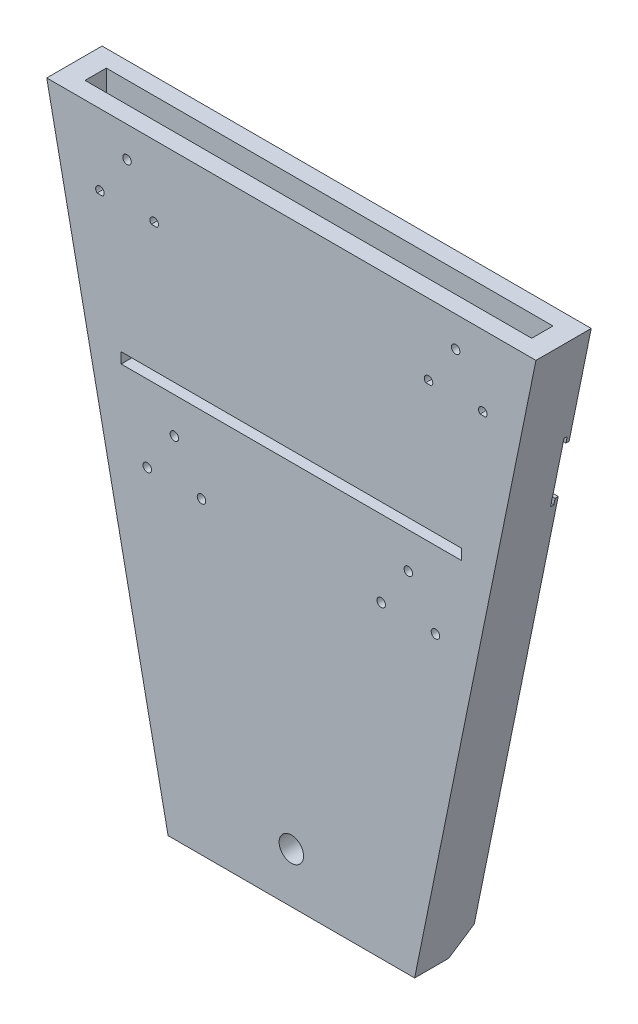
SolidWorks part; units mm, degrees
ref_plane "前视基准面" through (0, 0, 0) normal (0, 0, 1) x (1, 0, 0)
ref_plane "上视基准面" through (0, 0, 0) normal (0, 1, 0) x (1, 0, 0)
ref_plane "右视基准面" through (0, 0, 0) normal (1, 0, 0) x (0, 0, -1)
other "Configuration Table"
sketch "草图1" plane through (0, 0, 0) normal (0, 0, 1) x (1, 0, 0)
  line L0 (-60, 0) -> (60, 0)
  line L1 (0, 77.3448) -> (0, -71.5734) construction
  line L2 (-115, 270) -> (115, 270)
  line L3 (-115, 270) -> (-60, 0)
  line L4 (115, 270) -> (60, 0)
  point P3 (0, 0)
  point P8 (0, 270)
  dimension "D1" = 120
  dimension "D2" = 230
  dimension "D3" = 270
extrude "凸台-拉伸1" add sketch "草图1" along normal blind 8
sketch "草图2" plane through (0, 0, 8) normal (0, 0, 1) x (1, 0, 0)
  line L0 (-60, 0) -> (60, 0) construction
  line L1 (0, -1000) -> (0, 0.3) construction
  line L2 (0, 26.71) -> (0, 57.7278) construction
  line L3 (0.005, 0.31) -> (0, 0.3)
  line L4 (0, 26.71) -> (12.1089, 26.71)
  line L6 (0, 0.3) -> (17.4887, 0.3)
  line L7 (12.1089, 26.71) -> (17.4887, 0.3)
  line L8 (-115, 270) -> (-60, 0) construction
  arc A0 (0, 26.71) -> (0.005, 0.31) centre (0, 13.51) ccw
  dimension "D1" = 26.4
  dimension "D2" = 13.51
  dimension "D3" = 14.5
  dimension "D5" = 13.21
extrude "切除-拉伸1" cut sketch "草图2" against normal blind 8.6
sketch "草图3" plane through (0, 0, 8) normal (0, 0, 1) x (1, 0, 0)
  line L0 (-94.3261, 168.51) -> (94.3261, 168.51)
  line L1 (-115, 270) -> (-60, 0) construction
  line L2 (60, 0) -> (115, 270) construction
  line L4 (-96.3631, 178.51) -> (96.3631, 178.51)
  line L5 (-107.8704, 235) -> (107.8704, 235)
  point P0 (-115, 270)
  point P14 (0, 178.51)
  point P15 (0, 13.51)
  dimension "D1" = 155
  dimension "D2" = 10
  dimension "D3" = 35
sketch "草图5" plane through (0, 0, 0) normal (0, 0, -1) x (-1, 0, 0)
  line L4 (60, 0) -> (115, 270)
  line L5 (115, 270) -> (-115, 270)
  line L6 (-115, 270) -> (-60, 0)
  line L7 (-60, 0) -> (60, 0)
  line L8 (60, 0) -> (115, 270)
  line L9 (115, 270) -> (-115, 270)
  line L10 (-115, 270) -> (-60, 0)
  line L11 (-60, 0) -> (60, 0)
  dimension "D1" = 0
extrude "凸台-拉伸2" add sketch "草图5" along normal blind 8
sketch "草图6" plane through (0, 0, 8) normal (0, 0, 1) x (1, 0, 0)
  line L4 (-115, 270) -> (-60, 0)
  line L5 (-60, 0) -> (60, 0)
  line L6 (60, 0) -> (115, 270)
  line L7 (115, 270) -> (-115, 270)
  line L8 (-115, 270) -> (-60, 0)
  line L9 (-60, 0) -> (60, 0)
  line L10 (60, 0) -> (115, 270)
  line L11 (115, 270) -> (-115, 270)
  point P2 (0, 13.51)
  dimension "D1" = 0
extrude "凸台-拉伸3" add sketch "草图6" along normal blind 10
sketch "草图7" plane through (0, 0, 18) normal (0, 0, 1) x (1, 0, 0)
  circle A0 centre (0, 13.51) radius 5.75
  dimension "D1" = 11.5
extrude "切除-拉伸2" cut sketch "草图7" against normal blind 22
ref_plane "基准面1" through (0, 0, 18) normal (0, 0, 1) x (1, 0, 0)
sketch "草图9" plane through (0, 0, 18) normal (0, 0, 1) x (1, 0, 0)
  line L0 (-60, 0) -> (60, 0)
  line L1 (60, 0) -> (57.963, -10)
  line L2 (57.963, -10) -> (-57.963, -10)
  line L3 (-57.963, -10) -> (-60, 0)
  line L4 (60, 0) -> (115, 270) construction
  line L5 (-115, 270) -> (-60, 0) construction
  line L6 (60, 0) -> (115, 270)
  line L7 (-115, 270) -> (-60, 0)
  dimension "D1" = 10
extrude "凸台-拉伸5" add sketch "草图9" against normal blind 26 contours L3 L2 L1 L0 region at (0, -4.9712, 18)
ref_plane "基准面2" through (0, 0, -8) normal (0, 0, 1) x (1, 0, 0)
sketch "草图11" plane through (0, 0, -8) normal (0, 0, 1) x (1, 0, 0)
  line L0 (110.9179, 270) -> (53.8808, -10)
  line L1 (-110.9179, 270) -> (-53.8808, -10)
  line L2 (109.6932, 270) -> (52.6562, -10)
  line L3 (-109.6932, 270) -> (-52.6562, -10)
  line L4 (115, 270) -> (-115, 270)
  line L5 (-115, 270) -> (-57.963, -10)
  line L6 (-57.963, -10) -> (57.963, -10)
  line L7 (57.963, -10) -> (115, 270)
  line L8 (115, 270) -> (-115, 270)
  line L9 (-115, 270) -> (-57.963, -10)
  line L10 (-57.963, -10) -> (57.963, -10)
  line L11 (57.963, -10) -> (115, 270)
  dimension "D2" = 4
  dimension "D3" = 4
  dimension "D4" = 1.2
  dimension "D5" = 1.2
  dimension "D1" = 0
sketch "草图12" plane through (0, 0, -8) normal (0, 0, 1) x (1, 0, 0)
  line L0 (-115, 270) -> (-60, 0) construction
  line L1 (60, 0) -> (115, 270) construction
  line L2 (-115, 270) -> (-60, 0)
  line L3 (60, 0) -> (115, 270)
  line L4 (60, 0) -> (-60, 0)
  line L5 (57.963, -10) -> (60, 0)
  line L6 (-57.963, -10) -> (57.963, -10)
  line L7 (-60, 0) -> (-57.963, -10)
  line L8 (60, 0) -> (-60, 0)
  line L9 (57.963, -10) -> (60, 0)
  line L10 (-57.963, -10) -> (57.963, -10)
  line L11 (-60, 0) -> (-57.963, -10)
  line L12 (-109.6932, 270) -> (-52.6562, -10) construction
  line L13 (109.6932, 270) -> (52.6562, -10) construction
  line L14 (-110.9179, 270) -> (-53.8808, -10) construction
  line L15 (110.9179, 270) -> (53.8808, -10) construction
  line L16 (115, 270) -> (-115, 270)
  line L17 (-115, 270) -> (-57.963, -10)
  line L18 (-57.963, -10) -> (57.963, -10)
  line L19 (57.963, -10) -> (115, 270)
  line L20 (115, 270) -> (-115, 270)
  line L21 (-115, 270) -> (-57.963, -10)
  line L22 (-57.963, -10) -> (57.963, -10)
  line L23 (57.963, -10) -> (115, 270)
  line L24 (-109.6932, 270) -> (-52.6562, -10)
  line L25 (109.6932, 270) -> (52.6562, -10)
  line L26 (-110.9179, 270) -> (-53.8808, -10)
  line L27 (110.9179, 270) -> (53.8808, -10)
  dimension "D1" = 0
  dimension "D2" = 0
extrude "切除-拉伸4" cut sketch "草图12" along normal blind 21 contours L25 L8 L24 L22 region at (0, -4.9684, -8)
chamfer "倒角6" distance 5 angle 45 1 edges at (0, 0, -8)
chamfer "倒角8" distance 10 angle 45 2 edges at (-55.3096, -10, -8) (55.3096, -10, -8)
sketch "草图13" plane through (0, 270, 0) normal (0, 1, 0) x (1, 0, 0)
  line L1 (-105, 0) -> (105, 0)
  line L2 (-105, 0) -> (-105, -10)
  line L3 (-105, -10) -> (105, -10)
  line L4 (105, 0) -> (105, -10)
  line L5 (-105, 0) -> (105, -10) construction
  line L6 (-105, -10) -> (105, 0) construction
  line L7 (115, -18) -> (-115, -18) construction
  line L9 (-115, -18) -> (-115, 8) construction
  point P4 (0, -5)
  dimension "D1" = 210
  dimension "D2" = 10
  dimension "D3" = 13
  dimension "D4" = 115
extrude "切除-拉伸5" cut sketch "草图13" against normal blind 15
sketch "草图14" plane through (0, 0, 18) normal (0, 0, 1) x (1, 0, 0)
  line L0 (-96.3631, 178.51) -> (96.3631, 178.51) construction
  line L1 (-96.3631, 178.51) -> (96.3631, 178.51)
  line L2 (-94.3261, 168.51) -> (94.3261, 168.51) construction
  line L3 (-107.8704, 235) -> (107.8704, 235) construction
  line L4 (115, 270) -> (-115, 270)
  line L5 (-115, 270) -> (-57.963, -10)
  line L6 (-57.963, -10) -> (57.963, -10)
  line L7 (57.963, -10) -> (115, 270)
  line L8 (115, 270) -> (-115, 270)
  line L9 (-115, 270) -> (-57.963, -10)
  line L10 (-57.963, -10) -> (57.963, -10)
  line L11 (57.963, -10) -> (115, 270)
  line L12 (-94.3261, 168.51) -> (94.3261, 168.51)
  line L13 (-107.8704, 235) -> (107.8704, 235)
  line L14 (0, 270) -> (0, -10) construction
  line L15 (-80, 176.01) -> (80, 176.01)
  line L16 (-80, 176.01) -> (-80, 171.01)
  line L17 (-80, 171.01) -> (80, 171.01)
  line L18 (80, 176.01) -> (80, 171.01)
  line L19 (-80, 176.01) -> (80, 171.01) construction
  line L20 (-80, 171.01) -> (80, 176.01) construction
  point P14 (0, 173.51)
  dimension "D2" = 160
  dimension "D3" = 5
  dimension "D4" = 5
  dimension "D1" = 0
extrude "切除-拉伸6" cut sketch "草图14" against normal blind 10 contours L18 L15 L16 L17 region at (0, 173.51, 18)
sketch "草图16" plane through (0, 0, 18) normal (0, 0, 1) x (1, 0, 0)
  line L0 (0, 270) -> (0, -27.9065) construction
  line L2 (115, 270) -> (-115, 270) construction
  line L3 (-107.8704, 235) -> (107.8704, 235) construction
  line L4 (-94.3261, 168.51) -> (94.3261, 168.51) construction
  line L5 (-96.3631, 178.51) -> (96.3631, 178.51) construction
  line L6 (115, 270) -> (-115, 270)
  line L7 (-107.8704, 235) -> (107.8704, 235)
  line L8 (-94.3261, 168.51) -> (94.3261, 168.51)
  line L9 (-96.3631, 178.51) -> (96.3631, 178.51)
  line L11 (-90.2182, 178.51) -> (90.2182, 178.51)
  line L12 (-90.2182, 178.51) -> (-90.2182, 168.51)
  line L13 (-90.2182, 168.51) -> (90.2182, 168.51)
  line L14 (90.2182, 178.51) -> (90.2182, 168.51)
  line L15 (-90.2182, 178.51) -> (90.2182, 168.51) construction
  line L16 (-90.2182, 168.51) -> (90.2182, 178.51) construction
  circle A0 centre (-77.25, 255.6426) radius 2
  circle A1 centre (-90, 236.5) radius 2
  circle A2 centre (-64.5, 236.5) radius 2
  circle A3 centre (64.5, 236.5) radius 2
  circle A4 centre (90, 236.5) radius 2
  circle A5 centre (77.25, 255.6426) radius 2
  circle A6 centre (-55, 154.1526) radius 2
  circle A7 centre (-67.75, 135.01) radius 2
  circle A8 centre (-42.25, 135.01) radius 2
  circle A9 centre (42.25, 135.01) radius 2
  circle A10 centre (67.75, 135.01) radius 2
  circle A11 centre (55, 154.1526) radius 2
  point P15 (0, 173.51)
  dimension "D6" = 4
  dimension "D7" = 4
  dimension "D8" = 4
  dimension "D15" = 4
  dimension "D16" = 4
  dimension "D17" = 4
  dimension "D1" = 33.5
  dimension "D2" = 33.5
  dimension "D3" = 25.5
  dimension "D4" = 23
  dimension "D5" = 23
  dimension "D9" = 90
  dimension "D10" = 23
  dimension "D11" = 23
  dimension "D12" = 25.5
  dimension "D13" = 33.5
  dimension "D14" = 33.5
  dimension "D18" = 55
extrude "切除-拉伸7" cut sketch "草图16" against normal blind 10 contours A0 | A1 | A2 | A5 | A3 | A4 | A6 | A8 | A11 | A9 | A10 | A7 region at (-90, 236.6324, 18) region at (90, 236.6324, 18) region at (64.5, 236.6324, 18) region at (-64.5, 236.6324, 18) region at (-77.25, 255.6426, 18) region at (77.25, 255.6426, 18) region at (-55, 154.1526, 18) region at (-42.25, 135.01, 18) region at (42.25, 135.01, 18) region at (67.75, 135.01, 18) region at (55, 154.1526, 18)
sketch "草图17" plane through (0, 0, 18) normal (0, 0, 1) x (1, 0, 0)
  point P0 (-60.2489, 215.8027)
  point P2 (-96.3631, 178.51)
sketch "草图18" plane through (0, 0, 0) normal (0, -1, 0) x (1, 0, 0)
  line L4 (-54.6932, 13) -> (-54.6932, -3)
  line L5 (-54.6932, -3) -> (54.6932, -3)
  line L6 (54.6932, -3) -> (54.6932, 13)
  line L7 (54.6932, 13) -> (-54.6932, 13)
  line L8 (-54.6932, 13) -> (-54.6932, -3)
  line L10 (54.6932, -3) -> (54.6932, 13)
  line L11 (54.6932, 13) -> (-54.6932, 13)
  line L13 (-54.6932, -3) -> (54.6932, -3)
  dimension "D1" = 0
extrude "凸台-拉伸7" add sketch "草图18" along normal blind 2
chamfer "倒角10" distance 2 angle 45 1 edges at (0, -2, -3)
sketch "草图32" plane through (0, 0, -8) normal (0, 0, -1) x (-1, 0, 0)
  line L0 (-96.3631, 178.51) -> (-96.3631, 232.5516) construction
  line L2 (-96.3631, 218.8405) -> (3.6369, 218.8405)
  line L3 (-96.3631, 218.8405) -> (-96.3631, 193.8405)
  line L4 (-96.3631, 193.8405) -> (3.6369, 193.8405)
  line L5 (3.6369, 218.8405) -> (3.6369, 193.8405)
  line L6 (-96.3631, 218.8405) -> (3.6369, 193.8405) construction
  line L7 (-96.3631, 193.8405) -> (3.6369, 218.8405) construction
  line L8 (55.7117, 5) -> (54.6932, 0)
  line L9 (54.6932, 0) -> (60, 0)
  line L10 (60, 0) -> (115, 270)
  line L11 (115, 270) -> (-115, 270)
  line L12 (-115, 270) -> (-60, 0)
  line L13 (-60, 0) -> (-54.6932, 0)
  line L14 (-54.6932, 0) -> (-55.7117, 5)
  line L15 (-55.7117, 5) -> (55.7117, 5)
  line L16 (55.7117, 5) -> (54.6932, 0)
  line L17 (54.6932, 0) -> (60, 0)
  line L18 (60, 0) -> (115, 270)
  line L19 (115, 270) -> (-115, 270)
  line L20 (-115, 270) -> (-60, 0)
  line L21 (-60, 0) -> (-54.6932, 0)
  line L22 (-54.6932, 0) -> (-55.7117, 5)
  line L23 (-55.7117, 5) -> (55.7117, 5)
  point P14 (-46.3631, 206.3405)
  dimension "D2" = 100
  dimension "D3" = 25
  dimension "D1" = 0
extrude "切除-拉伸16" cut sketch "草图32" against normal blind 3 contours L5 L2 L3 L4 region at (46.3631, 206.3405, -8)
sketch "草图33" plane through (-3.6369, 0, 0) normal (1, 0, 0) x (0, 0, -1)
  line L4 (8, 193.8405) -> (8, 218.8405)
  line L5 (8, 218.8405) -> (5, 218.8405)
  line L6 (5, 218.8405) -> (5, 193.8405)
  line L7 (5, 193.8405) -> (8, 193.8405)
  line L8 (8, 193.8405) -> (8, 218.8405)
  line L9 (8, 218.8405) -> (5, 218.8405)
  line L10 (5, 218.8405) -> (5, 193.8405)
  line L11 (5, 193.8405) -> (8, 193.8405)
  dimension "D1" = 0
extrude "切除-拉伸17" cut sketch "草图33" along normal blind 1003
sketch "草图34" plane through (-3.6369, 0, 0) normal (1, 0, 0) x (0, 0, -1)
  line L0 (5, 193.8405) -> (8, 193.8405) construction
  line L1 (5, 218.8405) -> (6.5, 218.8405)
  line L2 (5, 218.8405) -> (5, 193.8405)
  line L3 (5, 193.8405) -> (6.5, 193.8405)
  line L4 (6.5, 218.8405) -> (6.5, 193.8405)
  line L5 (5, 218.8405) -> (6.5, 193.8405) construction
  line L6 (5, 193.8405) -> (6.5, 218.8405) construction
  point P4 (5.75, 206.3405)
extrude "切除-拉伸19" cut sketch "草图34" against normal blind 3
sketch "草图36" plane through (0, 218.8405, 0) normal (0, -1, 0) x (1, 0, 0)
  line L1 (-6.6369, -5) -> (104.5786, -5)
  line L2 (-6.6369, -5) -> (-6.6369, -6.5)
  line L3 (-6.6369, -6.5) -> (104.5786, -6.5)
  line L4 (104.5786, -5) -> (104.5786, -6.5)
  line L5 (-6.6369, -5) -> (104.5786, -6.5) construction
  line L6 (-3.6369, -8) -> (104.5786, -8)
  line L7 (104.5786, -8) -> (104.5786, -5)
  line L8 (104.5786, -5) -> (-6.6369, -5)
  line L9 (-6.6369, -5) -> (-6.6369, -6.5)
  line L10 (-6.6369, -6.5) -> (-3.6369, -6.5)
  line L11 (-3.6369, -6.5) -> (-3.6369, -8)
  line L12 (-3.6369, -8) -> (104.5786, -8) construction
  line L13 (104.5786, -8) -> (104.5786, -5) construction
  line L14 (104.5786, -5) -> (-6.6369, -5) construction
  line L15 (-6.6369, -5) -> (-6.6369, -6.5) construction
  line L16 (-6.6369, -6.5) -> (-3.6369, -6.5) construction
  line L17 (-3.6369, -6.5) -> (-3.6369, -8) construction
  line L18 (-6.6369, -6.5) -> (104.5786, -5) construction
  point P4 (48.9709, -5.75)
  dimension "D1" = 0
extrude "切除-拉伸20" cut sketch "草图36" against normal blind 3
sketch "草图37" plane through (0, 193.8405, 0) normal (0, 1, 0) x (1, 0, 0)
  line L1 (-6.6369, 5) -> (99.486, 5)
  line L2 (-6.6369, 5) -> (-6.6369, 6.5)
  line L3 (-6.6369, 6.5) -> (99.486, 6.5)
  line L4 (99.486, 5) -> (99.486, 6.5)
  line L5 (-6.6369, 5) -> (99.486, 6.5) construction
  line L6 (99.486, 8) -> (-3.6369, 8)
  line L7 (-3.6369, 8) -> (-3.6369, 6.5)
  line L8 (-3.6369, 6.5) -> (-6.6369, 6.5)
  line L9 (-6.6369, 6.5) -> (-6.6369, 5)
  line L10 (-6.6369, 5) -> (99.486, 5)
  line L11 (99.486, 5) -> (99.486, 8)
  line L12 (99.486, 8) -> (-3.6369, 8) construction
  line L13 (-3.6369, 8) -> (-3.6369, 6.5)
  line L14 (-3.6369, 6.5) -> (-6.6369, 6.5)
  line L15 (-6.6369, 6.5) -> (-6.6369, 5) construction
  line L16 (-6.6369, 5) -> (99.486, 5) construction
  line L17 (99.486, 5) -> (99.486, 8) construction
  line L18 (-6.6369, 6.5) -> (99.486, 5) construction
  point P4 (46.4246, 5.75)
  line M9 (-3.6369, 6.5) -> (-6.6369, 6.5)
  line M10 (-6.6369, 6.5) -> (-6.6369, 5)
  line M11 (-6.6369, 5) -> (99.486, 5)
  line M12 (99.486, 5) -> (99.486, 8)
  dimension "D1" = 0
extrude "切除-拉伸21" cut sketch "草图37" against normal blind 3 contours L3 M9 M10 M11 M12 region at (46.4246, 193.8405, -5.75)
sketch "草图38" plane through (-6.6369, 0, 0) normal (1, 0, 0) x (0, 0, -1)
  line L4 (5, 221.8405) -> (5, 190.8405)
  line L5 (5, 190.8405) -> (6.5, 190.8405)
  line L6 (6.5, 190.8405) -> (6.5, 221.8405)
  line L7 (6.5, 221.8405) -> (5, 221.8405)
  line L8 (5, 221.8405) -> (5, 190.8405)
  line L9 (5, 190.8405) -> (6.5, 190.8405)
  line L10 (6.5, 190.8405) -> (6.5, 221.8405)
  line L11 (6.5, 221.8405) -> (5, 221.8405)
  dimension "D1" = 0
extrude "切除-拉伸22" cut sketch "草图38" along normal blind 1003
